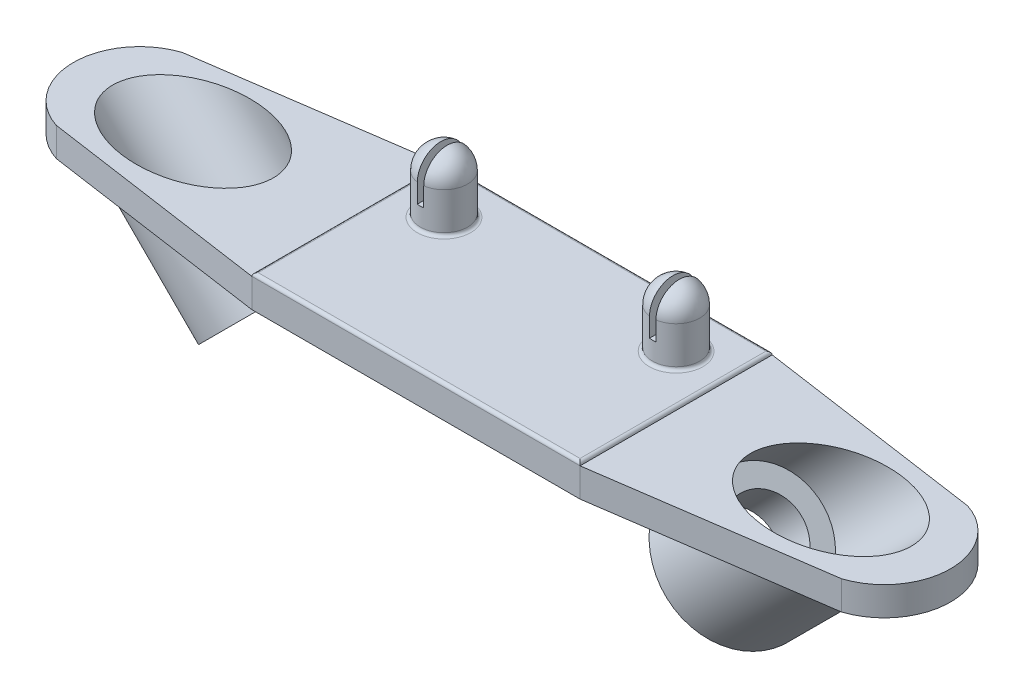
SolidWorks part; units mm, degrees
ref_plane "Front Plane" through (0, 0, 0) normal (0, 0, 1) x (1, 0, 0)
ref_plane "Top Plane" through (0, 0, 0) normal (0, 1, 0) x (1, 0, 0)
ref_plane "Right Plane" through (0, 0, 0) normal (1, 0, 0) x (0, 0, -1)
sketch "Sketch1" plane through (0, 0, 0) normal (0, 1, 0) x (1, 0, 0)
  line L0 (0, -6) -> (0, 6) construction
  line L1 (-10.25, -6) -> (10.25, -6)
  line L2 (-10.25, -6) -> (-10.25, 6)
  line L3 (-10.25, 6) -> (10.25, 6)
  line L4 (10.25, -6) -> (10.25, 6)
  line L5 (-10.25, -6) -> (10.25, 6) construction
  line L6 (-10.25, 6) -> (10.25, -6) construction
  point P0 (0, 0)
  dimension "D1" = 12
  dimension "D2" = 20.5
extrude "Boss-Extrude2" add sketch "Sketch1" along normal blind 2
sketch "Sketch2" plane through (0, 2, 0) normal (0, 1, 0) x (1, 0, 0)
  line L0 (10.25, 6) -> (-10.25, 6) construction
  line L1 (-10.25, 6) -> (-10.25, -6) construction
  line L2 (0, 6) -> (0, -6) construction
  line L3 (-10.25, -6) -> (10.25, -6) construction
  circle A0 centre (-7.25, 3) radius 1.475
  circle A1 centre (7.25, 3) radius 1.475
  dimension "D3" = 2.95
  dimension "D1" = 3
  dimension "D2" = 3
extrude "Boss-Extrude3" add sketch "Sketch2" along normal blind 4
fillet "Fillet1" radius 1.475 2 edges at (7.25, 6, -4.475) (-7.25, 6, -1.525)
fillet "Fillet2" radius 0.2 6 edges at (0, 2, 6) (-10.25, 2, 0) (0, 2, -6) (10.25, 2, 0) (-7.25, 2, -4.475) (7.25, 2, -4.475)
sketch "Sketch3" plane through (0, 0, 0) normal (0, -1, 0) x (1, 0, 0)
  line L1 (10.25, 6) -> (10.25, -6) construction
  line L3 (10.25, 0) -> (27.3883, 0) construction
  line L5 (10.25, -6) -> (24.518, -3.9393)
  line L7 (10.25, -6) -> (10.25, 0)
  line L8 (10.25, 0) -> (10.25, 6)
  line L9 (10.25, 6) -> (24.518, 3.9393)
  arc A2 (24.518, 3.9393) -> (24.518, -3.9393) centre (23.25, 0) cw
  dimension "D1" = 13
extrude "Boss-Extrude4" add sketch "Sketch3" against normal blind 1.8
mirror "Mirror1" about plane through (0, 0, 0) normal (1, 0, 0) of "Boss-Extrude4"
sketch "Sketch4" plane through (0, 0, 0) normal (0, 0, 1) x (1, 0, 0)
  line L0 (18.12, 0) -> (14.0683, -4.0517) construction
  line L1 (24.518, 0) -> (10.25, 0) construction
  line L2 (14.0683, -4.0517) -> (17.2503, -7.2337)
  line L3 (17.2503, -7.2337) -> (24.484, 0)
  line L4 (24.484, 0) -> (18.12, 0)
  line L5 (18.12, 0) -> (14.0683, -4.0517)
  dimension "D1" = 18.12
  dimension "D2" = 45
  dimension "D3" = 5.73
  dimension "D4" = 4.5
revolve "Revolve2" add sketch "Sketch4" angle 360 about L0
mirror "Mirror2" about plane through (0, 0, 0) normal (1, 0, 0) of "Revolve2"
sketch "Sketch5" plane through (1.0583, 0, 7.3276) normal (0.1429, 0, 0.9897) x (0.9897, 0, -0.1429)
sketch "Sketch6" plane through (5.0083, 5.0083, 0) normal (-0.7071, -0.7071, 0) x (0, 0, 1)
  circle A0 centre (0, -12.8128) radius 2.25
  dimension "D1" = 4.5
extrude "Cut-Extrude1" cut sketch "Sketch6" along normal through all both and the other way through all
mirror "Mirror3" about plane through (0, 0, 0) normal (1, 0, 0) of "Cut-Extrude1"
sketch "Sketch7" plane through (0, 0, 0) normal (0, 0, 1) x (1, 0, 0)
  line L1 (29.056, 8.287) -> (10.25, 8.287)
  line L2 (29.056, 8.287) -> (29.056, 1.8)
  line L3 (29.056, 1.8) -> (10.25, 1.8)
  line L4 (10.25, 8.287) -> (10.25, 1.8)
extrude "Cut-Extrude2" cut sketch "Sketch7" along normal through all both and the other way through all
mirror "Mirror4" about plane through (0, 0, 0) normal (1, 0, 0) of "Cut-Extrude2"
sketch "Sketch11" plane through (0, 1.8, 0) normal (0, 1, 0) x (1, 0, 0)
  line L0 (-23.102, 0) -> (-27.3883, 0) construction
  line L1 (-23.102, -4.1438) -> (-23.102, 4.1438) construction
  line L2 (-24.518, -3.9393) -> (-10.25, -6) construction
  line L3 (-10.25, 6) -> (-24.518, 3.9393) construction
  arc A0 (-24.518, 3.9393) -> (-24.518, -3.9393) centre (-23.25, 0) ccw construction
  ellipse E0 centre (-19.92, 0) end of major axis (-23.102, 0) minor radius 2.25 construction
ref_plane "Plane2" through (-12.451, 12.451, 0) normal (0.7071, -0.7071, 0) x (0, 0, -1)
sketch "Sketch14" plane through (-12.451, 12.451, 0) normal (0.7071, -0.7071, 0) x (0, 0, -1)
  circle A0 centre (0, -12.8128) radius 3.55
  dimension "D1" = 7.1
extrude "Cut-Extrude4" cut sketch "Sketch14" along normal blind 8
extrude "Cut-Extrude5" cut sketch "Sketch14" against normal blind 6
mirror "Mirror5" about plane through (0, 0, 0) normal (1, 0, 0) of "Cut-Extrude5", "Cut-Extrude4"
sketch "Sketch15" plane through (0, 0, 6) normal (0, 0, 1) x (1, 0, 0)
  line L0 (-7.25, 1.8) -> (-7.25, 6) construction
  line L1 (10.25, 1.8) -> (-10.25, 1.8) construction
  line L2 (-10.25, 1.8) -> (-10.25, 0) construction
  line L3 (-10.05, 2) -> (10.05, 2) construction
  line L4 (-7.05, 6) -> (-7.45, 6)
  line L5 (-7.05, 6) -> (-7.05, 3.3333)
  line L6 (-7.05, 3.3333) -> (-7.45, 3.3333)
  line L7 (-7.45, 6) -> (-7.45, 3.3333)
  dimension "D1" = 3
  dimension "D2" = 0.2
  dimension "D3" = 0.2
  dimension "D4" = 4
  dimension "D5" = 2.6667
extrude "Cut-Extrude6" cut sketch "Sketch15" against normal through all both and the other way through all
mirror "Mirror6" about plane through (0, 0, 0) normal (1, 0, 0) of "Cut-Extrude6"
equation "\"`2\"=10"
